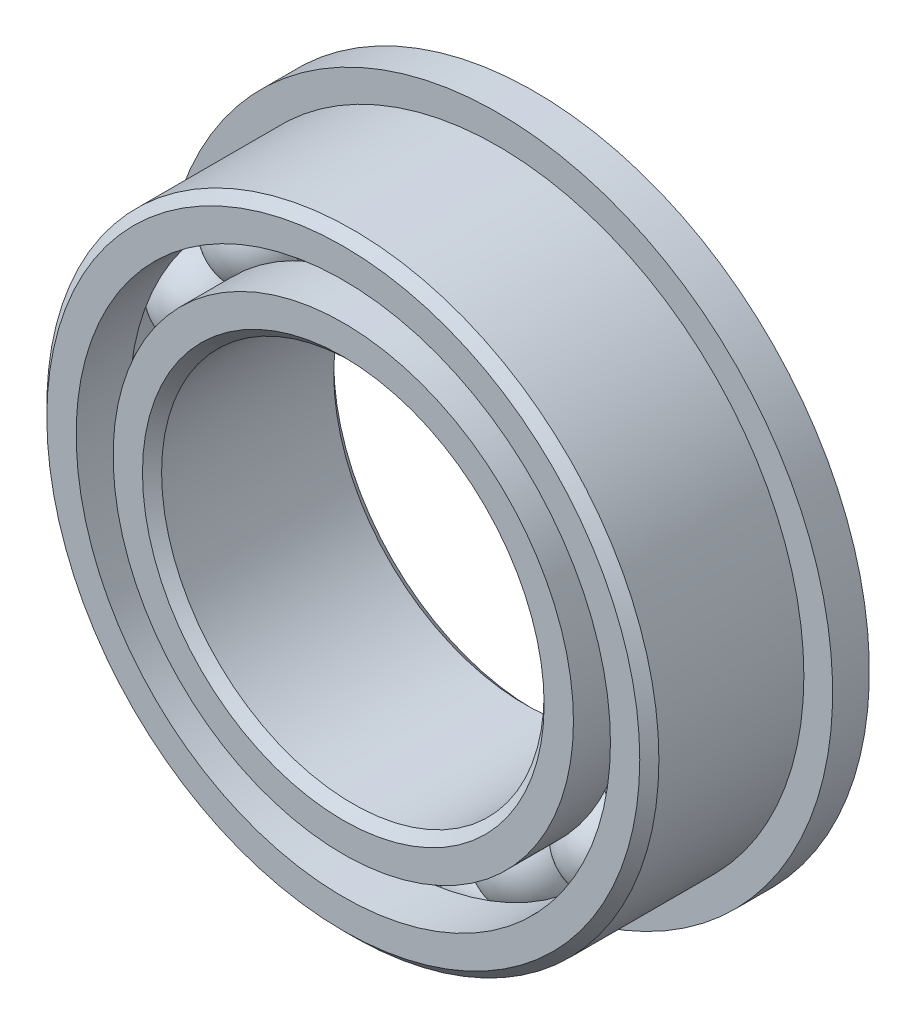
SolidWorks part; units mm, degrees
ref_plane "Front Plane" through (0, 0, 0) normal (0, 0, 1) x (1, 0, 0)
ref_plane "Top Plane" through (0, 0, 0) normal (0, 1, 0) x (1, 0, 0)
ref_plane "Right Plane" through (0, 0, 0) normal (1, 0, 0) x (0, 0, -1)
sketch "Sketch1" plane through (0, 0, 0) normal (1, 0, 0) x (0, 0, -1)
  line L0 (-1.9844, 0) -> (1.9844, 0) construction
  line L1 (0, 6.35) -> (0, -6.35) construction
  line L2 (1.7859, 6.35) -> (-1.7859, 6.35)
  line L3 (-1.7859, 6.35) -> (-1.9844, 6.1516)
  line L4 (-1.9844, 6.1516) -> (-1.9844, 5.5432)
  line L5 (-1.9844, 5.5432) -> (-0.8819, 5.5432)
  line L6 (1.9844, 5.5432) -> (0.8819, 5.5432)
  line L7 (1.9844, 6.1516) -> (1.9844, 5.5432)
  line L8 (1.7859, 6.35) -> (1.9844, 6.1516)
  line L9 (0, 6.35) -> (0, 5.1594) construction
  line L10 (0, 5.1594) -> (0, 3.9688) construction
  arc A0 (-0.8819, 5.5432) -> (0.8819, 5.5432) centre (0, 5.1594) cw
  point P14 (0, 3.9688)
  dimension "Width" = 3.9688
  dimension "OD" = 12.7
  dimension "D1" = 45
  dimension "D2" = 0.1984
  dimension "Shaft Dia" = 7.9375
  dimension "D3" = 1.7639
  dimension "D4" = 0.3838
revolve "Revolve1" add sketch "Sketch1" angle 360 about L0
sketch "Sketch3" plane through (0, 0, 0) normal (1, 0, 0) x (0, 0, -1)
  line L0 (-1.9844, 4.7756) -> (-0.8819, 4.7756)
  line L1 (0, 6.35) -> (0, -6.35) construction
  line L2 (-1.9844, 6.1516) -> (-1.9844, 5.5432) construction
  line L3 (-1.9844, 4.7756) -> (-1.9844, 4.1672)
  line L4 (-1.7859, 6.35) -> (-1.9844, 6.1516) construction
  line L5 (-1.9844, 4.1672) -> (-1.7859, 3.9688)
  line L6 (-1.7859, 3.9688) -> (1.7859, 3.9688)
  line L7 (1.7859, 6.35) -> (1.7859, -6.35) construction
  line L8 (1.7859, 3.9688) -> (1.9844, 4.1672)
  line L9 (1.9844, -6.1516) -> (1.9844, 6.1516) construction
  line L10 (1.9844, 4.1672) -> (1.9844, 4.7756)
  line L11 (1.9844, 4.7756) -> (0.8819, 4.7756)
  line L13 (1.7859, 6.35) -> (1.9844, 6.1516) construction
  arc A0 (0.8819, 5.5432) -> (-0.8819, 5.5432) centre (0, 5.1594) ccw construction
  arc A1 (0.8819, 4.7756) -> (-0.8819, 4.7756) centre (0, 5.1594) cw
revolve "Revolve3" add sketch "Sketch3" angle 360 about L0
sketch "Sketch4" plane through (0, 0, 0) normal (1, 0, 0) x (0, 0, -1)
  line L0 (-0.9618, 5.1594) -> (0.9618, 5.1594)
  arc A2 (-0.9618, 5.1594) -> (0.9618, 5.1594) centre (0, 5.1594) cw
  arc A3 (0.8819, 5.5432) -> (-0.8819, 5.5432) centre (0, 5.1594) ccw construction
revolve "Revolve4" add sketch "Sketch4" angle 360 about L0
ref_axis "Axis1" through (0, 0, -1.9844) along (0, 0, 1)
pattern_circular "CirPattern1" count 16 every 22.5 about axis through (0, 0, -1.9844) along (0, 0, 1) of bodies 104
sketch "Sketch5" plane through (0, 0, 0) normal (1, 0, 0) x (0, 0, -1)
  line L0 (-1.9844, 5.5432) -> (-0.8819, 5.5432) construction
  line L1 (-1.8852, 5.5432) -> (-0.9618, 5.5432)
  line L2 (-1.8852, 5.5432) -> (-1.8852, 4.7756)
  line L3 (-1.8852, 4.7756) -> (-0.9618, 4.7756)
  line L4 (-0.9618, 5.5432) -> (-0.9618, 4.7756)
  line L5 (-1.9844, 4.7756) -> (-0.8819, 4.7756) construction
  line L6 (1.9844, 5.5432) -> (0.8819, 5.5432) construction
  line L7 (1.8852, 5.5432) -> (0.9618, 5.5432)
  line L8 (1.8852, 5.5432) -> (1.8852, 4.7756)
  line L9 (1.8852, 4.7756) -> (0.9618, 4.7756)
  line L10 (0.9618, 5.5432) -> (0.9618, 4.7756)
  line L11 (1.9844, 4.7756) -> (0.8819, 4.7756) construction
  line L12 (-1.7859, 6.35) -> (-1.9844, 6.1516) construction
  point P18 (-1.8852, 6.2508)
revolve "Revolve5" [suppressed] add sketch "Sketch5" angle 360 about L0
sketch "Sketch6" plane through (0, 0, 0) normal (1, 0, 0) x (0, 0, -1)
  line L0 (1.9844, 0) -> (-1.9844, 0) construction
  line L1 (1.9844, 5.5432) -> (1.2224, 5.5432)
  line L2 (1.9844, 5.5432) -> (1.9844, 6.9469)
  line L3 (1.9844, 6.9469) -> (1.2224, 6.9469)
  line L4 (1.2224, 5.5432) -> (1.2224, 6.9469)
  dimension "Th" = 0.762
  dimension "Flange OD" = 13.8938
revolve "Revolve6" add sketch "Sketch6" angle 360 about L0
equation "\"D2@Sketch1\" = \"Width@Sketch1\"*.05"
equation "\"D3@Sketch1\" = \"Width@Sketch1\"/2.25"
equation "\"D4@Sketch1\" = (((\"OD@Sketch1\"-\"Width@Sketch1\")/2)/3.25)/3.5"
equation "\"D2@CirPattern1\" = 360/\"Balls@CirPattern1\""
